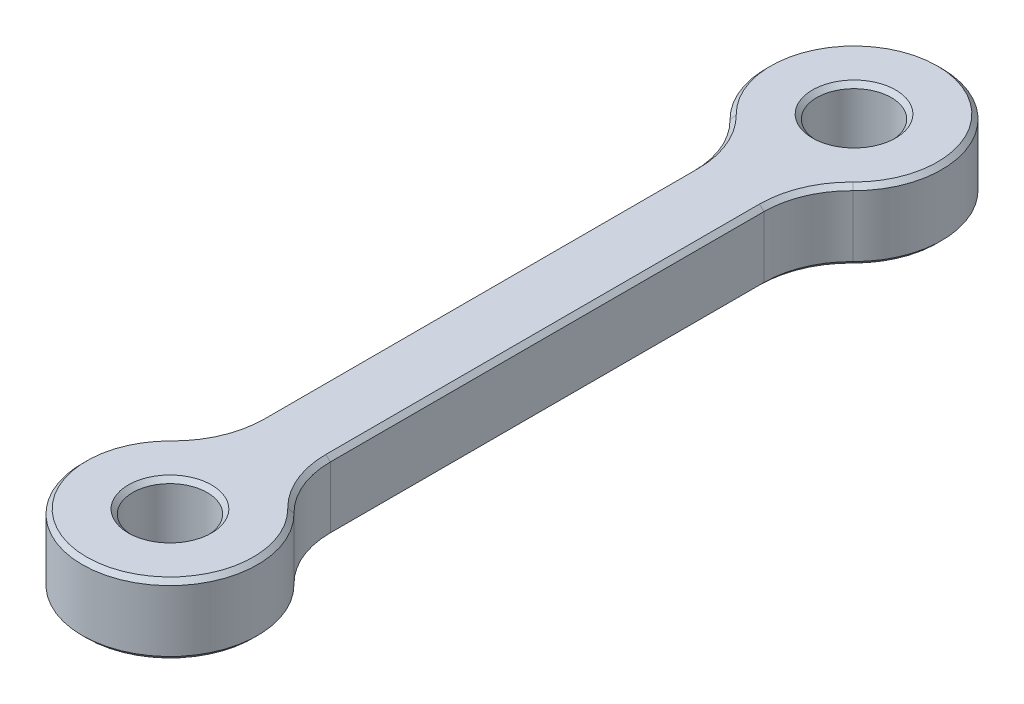
SolidWorks part; units mm, degrees
ref_plane "Front Plane" through (0, 0, 0) normal (0, 0, 1) x (1, 0, 0)
ref_plane "Top Plane" through (0, 0, 0) normal (0, 1, 0) x (1, 0, 0)
ref_plane "Right Plane" through (0, 0, 0) normal (1, 0, 0) x (0, 0, -1)
sketch "Sketch1" plane through (0, 0, 0) normal (0, 1, 0) x (1, 0, 0)
  line L0 (0, 39) -> (0, -39) construction
  line L1 (-4, 29.8348) -> (-4, -29.8348)
  line L2 (4, -29.8348) -> (4, 29.8348)
  circle A0 centre (0, 39) radius 4.25
  circle A1 centre (0, -39) radius 4.25
  arc A2 (4, 29.8348) -> (-4, 29.8348) centre (0, 39) ccw
  arc A3 (-4, -29.8348) -> (4, -29.8348) centre (0, -39) ccw
  dimension "D2" = 8.5
  dimension "D3" = 20
  dimension "D1" = 78
  dimension "D4" = 8
extrude "Boss-Extrude1" add sketch "Sketch1" along normal blind 8
fillet "Fillet1" radius 10 4 edges at (4, 4, 29.8348) (4, 4, -29.8348) (-4, 4, -29.8348) (-4, 4, 29.8348)
chamfer "Chamfer1" distance 0.5 angle 45 20 edges at (0, 0, 43.25) (0, 0, -34.75) (-4.7805, 0, -28.5901) (-4, 0, 0) (-4.7805, 0, 28.5901) (0, 0, 49) (4.7805, 0, 28.5901) (4, 0, 0) (4.7805, 0, -28.5901) (0, 0, -49) (0, 8, 43.25) (4.7805, 8, 28.5901) (0, 8, 49) (-4.7805, 8, 28.5901) (-4, 8, 0) (-4.7805, 8, -28.5901) (0, 8, -49) (4.7805, 8, -28.5901) (4, 8, 0) (0, 8, -34.75)
